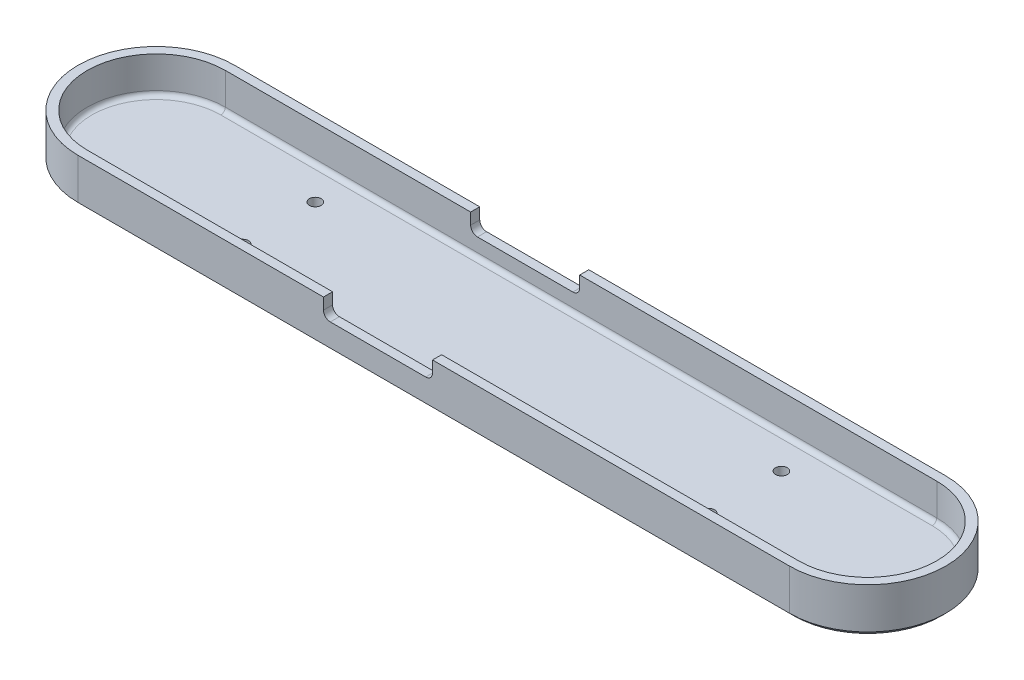
SolidWorks part; units mm, degrees
material "PLA"
ref_plane "Front Plane" through (0, 0, 0) normal (0, 0, 1) x (1, 0, 0)
ref_plane "Top Plane" through (0, 0, 0) normal (0, 1, 0) x (1, 0, 0)
ref_plane "Right Plane" through (0, 0, 0) normal (1, 0, 0) x (0, 0, -1)
sketch "Sketch1" plane through (0, 0, 0) normal (0, 1, 0) x (1, 0, 0)
  line L0 (-99.441, 0) -> (99.441, 0) construction
  line L1 (0, -55.9739) -> (0, 55.9739) construction
  line L2 (-99.441, 19.304) -> (99.441, 19.304)
  line L3 (-99.441, -19.304) -> (99.441, -19.304)
  arc A0 (-99.441, 19.304) -> (-99.441, -19.304) centre (-99.441, 0) ccw
  arc A1 (99.441, 19.304) -> (99.441, -19.304) centre (99.441, 0) cw
  circle A2 centre (-99.441, 0) radius 19.05 construction
  point P4 (0, 0)
  point P10 (0, 0)
  dimension "D2" = 0.254
  dimension "D3" = 38.1
  dimension "D1" = 198.882
extrude "MainBlock" add sketch "Sketch1" along normal blind 2.54
sketch "Sketch2" plane through (0, 0, 0) normal (0, -1, 0) x (1, 0, 0)
  line L0 (0, 0) -> (0, 50000) construction
  line L1 (-99.441, 21.844) -> (99.441, 21.844)
  line L2 (-99.441, -19.304) -> (99.441, -19.304)
  line L3 (99.441, 19.304) -> (-99.441, 19.304)
  line L5 (99.441, 19.304) -> (-99.441, 19.304)
  line L6 (-95.25, 0) -> (49904.75, 0) construction
  line L7 (99.441, -19.304) -> (-99.441, -19.304)
  line L8 (-99.441, -21.844) -> (99.441, -21.844)
  arc A0 (-99.441, 21.844) -> (-99.441, -21.844) centre (-99.441, 0) ccw
  arc A1 (99.441, 19.304) -> (99.441, -19.304) centre (99.441, 0) cw
  arc A2 (-99.441, 19.304) -> (-99.441, -19.304) centre (-99.441, 0) ccw
  arc A3 (99.441, -19.304) -> (99.441, 19.304) centre (99.441, 0) ccw
  arc A4 (-99.441, 19.304) -> (-99.441, -19.304) centre (-99.441, 0) ccw
  arc A6 (99.441, 21.844) -> (99.441, -21.844) centre (99.441, 0) cw
  point P0 (0, 19.304)
  point P15 (0, 21.844)
  point P16 (0, -19.304)
  point P19 (0, -21.844)
  dimension "D2" = 2.54
  dimension "2.1" = 43.688
  dimension "D1" = 0
extrude "Boss-Extrude1" add sketch "Sketch2" against normal blind 12.7
sketch "Sketch3" plane through (0, 0, 0) normal (0, -1, 0) x (1, 0, 0)
  line L0 (0, 0) -> (50000, 0) construction
  line L1 (0, 0) -> (0, 50000) construction
  line L2 (-99.441, 0.9216) -> (-99.441, 50000.9216) construction
  arc A0 (-99.441, 21.844) -> (-99.441, -21.844) centre (-99.441, 0) ccw construction
  arc A1 (-99.441, 21.844) -> (-99.441, -21.844) centre (-99.441, 0) ccw construction
  circle A2 centre (0, 10.16) radius 1.651 construction
  circle A3 centre (-65.151, 10.16) radius 1.651
  circle A4 centre (65.151, 10.16) radius 1.651
  circle A5 centre (65.151, -10.16) radius 1.651
  circle A6 centre (-65.151, -10.16) radius 1.651
  circle A7 centre (0, -10.16) radius 1.651 construction
  dimension "D1" = 3.302
  dimension "D4" = 3.302
  dimension "D2" = 10.16
  dimension "D3" = 10.16
  dimension "D5" = 34.29
extrude "Mount-Holes" cut sketch "Sketch3" against normal through all
fillet "Fillet1" radius 1.27 4 edges at (118.745, 2.54, 0) (0, 2.54, 19.304) (-118.745, 2.54, 0) (0, 2.54, -19.304)
chamfer "Chamfer1" distance 1.27 angle 45 4 edges at (0, 0, 21.844) (-121.285, 0, 0) (121.285, 0, 0) (0, 0, -21.844)
sketch "Sketch4" plane through (0, 12.7, 0) normal (0, 1, 0) x (1, 0, 0)
  line L0 (-30.861, 21.844) -> (-30.861, 19.304)
  line L1 (-99.441, 21.844) -> (99.441, 21.844) construction
  line L2 (-99.441, 19.304) -> (99.441, 19.304) construction
  line L3 (-30.861, 19.304) -> (-0.381, 19.304)
  line L4 (-0.381, 19.304) -> (-0.381, 21.844)
  line L5 (-0.381, 21.844) -> (-30.861, 21.844)
  line L6 (-15.621, 21.844) -> (-15.621, 19.304) construction
  line L7 (-99.441, 0) -> (-99.441, 21.844) construction
  arc A0 (-99.441, 19.304) -> (-99.441, -19.304) centre (-99.441, 0) ccw construction
  arc A1 (-99.441, 19.304) -> (-99.441, -19.304) centre (-99.441, 0) ccw construction
  dimension "D1" = 83.82
  dimension "D2" = 30.48
extrude "Stabilizer-Mount-Cutout" cut sketch "Sketch4" against normal blind 5.08
mirror "Mirror1" about plane through (0, 0, 0) normal (0, 0, 1) of "Stabilizer-Mount-Cutout"
fillet "Fillet2" radius 1.905 4 edges at (-0.381, 7.62, -20.574) (-30.861, 7.62, -20.574) (-30.861, 7.62, 20.574) (-0.381, 7.62, 20.574)
equation "\"D4@Sketch3\"=\"D1@Sketch3\""
